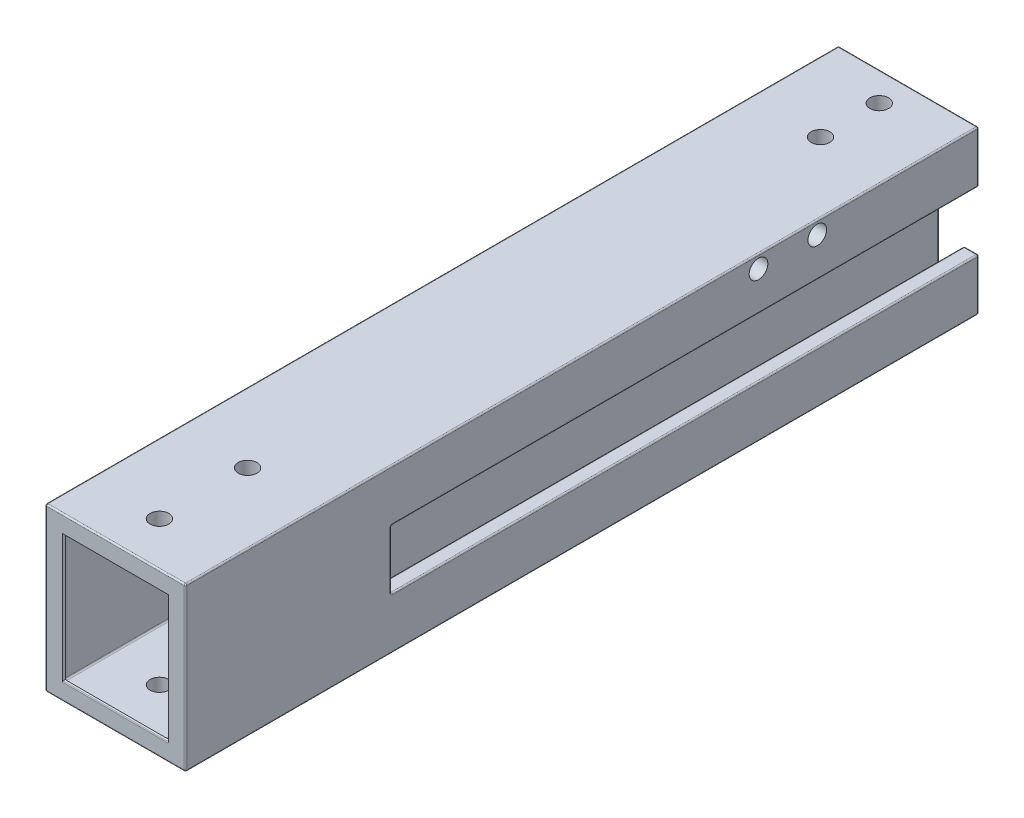
SolidWorks part; units mm, degrees
ref_plane "Front Plane" through (0, 0, 0) normal (0, 0, 1) x (1, 0, 0)
ref_plane "Top Plane" through (0, 0, 0) normal (0, 1, 0) x (1, 0, 0)
ref_plane "Right Plane" through (0, 0, 0) normal (1, 0, 0) x (0, 0, -1)
sketch "Sketch1" plane through (0, 0, 0) normal (0, 0, 1) x (1, 0, 0)
  line L0 (-6.35, -6.35) -> (-6.35, 48.95)
  line L1 (0, 0) -> (35.1, 0) construction
  line L2 (0, 0) -> (0, 42.6) construction
  line L3 (0, 42.6) -> (35.1, 42.6) construction
  line L4 (35.1, 0) -> (35.1, 42.6) construction
  line L5 (-6.35, 48.95) -> (41.45, 48.95)
  line L6 (41.45, -6.35) -> (41.45, 48.95)
  line L7 (-6.35, -6.35) -> (41.45, -6.35)
  dimension "D1" = 35.1
  dimension "D2" = 42.6
  dimension "D3" = 6.35
extrude "Boss-Extrude1" add sketch "Sketch1" against normal blind 270
sketch "Sketch2" plane through (0, 0, 0) normal (0, 0, 1) x (1, 0, 0)
  line L0 (35.1, 42.6) -> (0, 42.6)
  line L1 (0, 42.6) -> (0, 0)
  line L2 (0, 0) -> (35.1, 0)
  line L3 (35.1, 0) -> (35.1, 42.6)
  line L4 (-6.35, -6.35) -> (41.45, -6.35)
  line L5 (41.45, -6.35) -> (41.45, 48.95)
  line L6 (41.45, 48.95) -> (-6.35, 48.95)
  line L7 (-6.35, 48.95) -> (-6.35, -6.35)
  line L8 (-6.35, -6.35) -> (41.45, -6.35) construction
  line L9 (41.45, -6.35) -> (41.45, 48.95) construction
  line L10 (41.45, 48.95) -> (-6.35, 48.95) construction
  line L11 (-6.35, 48.95) -> (-6.35, -6.35) construction
  dimension "D1" = 0
  dimension "D2" = 6.35
extrude "Cut-Extrude1" cut sketch "Sketch2" against normal blind 60
sketch "Sketch3" plane through (0, -6.35, 0) normal (0, -1, 0) x (1, 0, 0)
  line L3 (-6.35, -270) -> (-6.35, 0) construction
  line L4 (-6.35, 0) -> (41.45, 0) construction
  line L5 (-6.35, -270) -> (41.45, -270) construction
  circle A0 centre (17.55, -15) radius 3.175
  circle A3 centre (17.55, -260) radius 3.175
  circle A5 centre (17.55, -240) radius 3.175
  circle A10 centre (17.55, -45) radius 3.175
  dimension "D5" = 30
  dimension "D10" = 6.35
  dimension "D11" = 6.35
  dimension "D7" = 6.35
  dimension "D12" = 6.35
  dimension "D6" = 23.9
  dimension "D8" = 30
  dimension "D9" = 23.9
  dimension "D2" = 15
  dimension "D3" = 10
  dimension "D13" = 23.9
  dimension "D14" = 23.9
extrude "Cut-Extrude2" cut sketch "Sketch3" against normal through all
sketch "Sketch8" plane through (0, 0, -270) normal (0, 0, -1) x (-1, 0, 0)
  line L0 (6.35, 21.3) -> (-41.45, 21.3) construction
  line L1 (6.35, 11.3) -> (1.35, 11.3)
  line L2 (1.35, 11.3) -> (1.35, 1.3)
  line L3 (1.35, 1.3) -> (-7.15, 1.3)
  line L4 (-41.45, -6.35) -> (6.35, -6.35)
  line L5 (6.35, -6.35) -> (6.35, 48.95)
  line L6 (6.35, 48.95) -> (-41.45, 48.95)
  line L7 (-41.45, 48.95) -> (-41.45, -6.35)
  line L8 (-41.45, -6.35) -> (6.35, -6.35) construction
  line L9 (6.35, -6.35) -> (6.35, 48.95) construction
  line L10 (6.35, 48.95) -> (-41.45, 48.95) construction
  line L11 (-41.45, 48.95) -> (-41.45, -6.35) construction
  line L12 (-7.15, 1.3) -> (-7.15, 41.3)
  line L13 (6.35, 31.3) -> (1.35, 31.3)
  line L14 (1.35, 31.3) -> (1.35, 41.3)
  line L15 (1.35, 41.3) -> (-7.15, 41.3)
  line L16 (-17.55, -6.35) -> (-17.55, 48.95) construction
  line L17 (-41.45, 11.3) -> (-36.45, 11.3)
  line L18 (-36.45, 11.3) -> (-36.45, 1.3)
  line L19 (-36.45, 1.3) -> (-27.95, 1.3)
  line L20 (-41.45, 31.3) -> (-36.45, 31.3)
  line L21 (-36.45, 41.3) -> (-27.95, 41.3)
  line L22 (-36.45, 31.3) -> (-36.45, 41.3)
  line L23 (-27.95, 1.3) -> (-27.95, 41.3)
  line L24 (6.35, 31.3) -> (6.35, 11.3)
  line L25 (-41.45, 31.3) -> (-41.45, 11.3)
  point P2 (6.35, 21.3)
  point P16 (-7.15, 21.3)
  dimension "D2" = 10
  dimension "D3" = 20
  dimension "D4" = 8.5
  dimension "D5" = 5
  dimension "D1" = 0
extrude "Cut-Extrude4" cut sketch "Sketch8" against normal blind 200
sketch "Sketch11" plane through (-6.35, 0, 0) normal (-1, 0, 0) x (0, 0, 1)
  line L2 (-270, 48.95) -> (0, 48.95) construction
  line L3 (-270, 48.95) -> (-270, 31.3) construction
  circle A4 centre (-215, 44.55) radius 3.175
  circle A5 centre (-195, 44.55) radius 3.175
  dimension "D2" = 6.35
  dimension "D3" = 6.35
  dimension "D1" = 55
  dimension "D4" = 20
  dimension "D5" = 4.4
  dimension "D6" = 75
extrude "Cut-Extrude5" cut sketch "Sketch11" against normal through all
sketch "Sketch12" plane through (0, 0, -270) normal (0, 0, -1) x (-1, 0, 0)
  line L0 (-41.45, 31.3) -> (-41.45, 11.3) construction
  line L1 (-9.55, 6.3) -> (-25.55, 6.3)
  line L2 (-9.55, 6.3) -> (-9.55, 36.3)
  line L3 (-9.55, 36.3) -> (-25.55, 36.3)
  line L4 (-25.55, 6.3) -> (-25.55, 36.3)
  line L20 (6.35, -6.35) -> (6.35, 11.3)
  line L21 (6.35, 11.3) -> (1.35, 11.3)
  line L22 (1.35, 11.3) -> (1.35, 1.3)
  line L23 (1.35, 1.3) -> (-7.15, 1.3)
  line L24 (-7.15, 1.3) -> (-7.15, 41.3)
  line L25 (-7.15, 41.3) -> (1.35, 41.3)
  line L26 (1.35, 41.3) -> (1.35, 31.3)
  line L27 (1.35, 31.3) -> (6.35, 31.3)
  line L28 (6.35, 31.3) -> (6.35, 48.95)
  line L29 (6.35, 48.95) -> (-41.45, 48.95)
  line L30 (-41.45, 48.95) -> (-41.45, 31.3)
  line L31 (-41.45, 31.3) -> (-36.45, 31.3)
  line L32 (-36.45, 31.3) -> (-36.45, 41.3)
  line L33 (-36.45, 41.3) -> (-27.95, 41.3)
  line L34 (-27.95, 41.3) -> (-27.95, 1.3)
  line L35 (-27.95, 1.3) -> (-36.45, 1.3)
  line L36 (-36.45, 1.3) -> (-36.45, 11.3)
  line L37 (-36.45, 11.3) -> (-41.45, 11.3)
  line L38 (-41.45, 11.3) -> (-41.45, -6.35)
  line L39 (-41.45, -6.35) -> (6.35, -6.35)
  line L40 (6.35, -6.35) -> (6.35, 11.3) construction
  line L41 (6.35, 11.3) -> (1.35, 11.3) construction
  line L42 (1.35, 11.3) -> (1.35, 1.3) construction
  line L43 (1.35, 1.3) -> (-7.15, 1.3) construction
  line L44 (-7.15, 1.3) -> (-7.15, 41.3) construction
  line L45 (-7.15, 41.3) -> (1.35, 41.3) construction
  line L46 (1.35, 41.3) -> (1.35, 31.3) construction
  line L47 (1.35, 31.3) -> (6.35, 31.3) construction
  line L48 (6.35, 31.3) -> (6.35, 48.95) construction
  line L49 (6.35, 48.95) -> (-41.45, 48.95) construction
  line L50 (-41.45, 48.95) -> (-41.45, 31.3) construction
  line L51 (-41.45, 31.3) -> (-36.45, 31.3) construction
  line L52 (-36.45, 31.3) -> (-36.45, 41.3) construction
  line L53 (-36.45, 41.3) -> (-27.95, 41.3) construction
  line L54 (-27.95, 41.3) -> (-27.95, 1.3) construction
  line L55 (-27.95, 1.3) -> (-36.45, 1.3) construction
  line L56 (-36.45, 1.3) -> (-36.45, 11.3) construction
  line L57 (-36.45, 11.3) -> (-41.45, 11.3) construction
  line L58 (-41.45, 11.3) -> (-41.45, -6.35) construction
  line L59 (-41.45, -6.35) -> (6.35, -6.35) construction
  point P10 (-25.55, 21.3)
  point P12 (-17.55, 6.3)
  point P14 (-41.45, 21.3)
  point P16 (-17.55, -6.35)
  dimension "D2" = 30
  dimension "D3" = 16
  dimension "D1" = 0
extrude "Cut-Extrude6" cut sketch "Sketch12" against normal blind 50
chamfer "Chamfer2" distance 0.5 angle 45 8 edges at (0, 21.3, 0) (17.55, 42.6, 0) (17.55, 0, 0) (35.1, 21.3, 0) (17.55, 36.3, -270) (25.55, 21.3, -270) (9.55, 21.3, -270) (17.55, 6.3, -270)
fillet "Fillet1" radius 0.5 77 edges at (17.55, 0, -60) (0, 21.3, -60) (17.55, 42.6, -60) (35.1, 21.3, -60) (41.45, 31.3, -170) (38.95, 31.3, -270) (36.45, 31.3, -170) (36.45, 36.3, -270) (36.45, 41.3, -170) (32.2, 41.3, -270) (36.45, 6.3, -270) (36.45, 1.3, -170) (32.2, 1.3, -270) (41.45, 11.3, -170) (36.45, 11.3, -170) (38.95, 11.3, -270) (27.95, 1.3, -170) (27.95, 41.3, -170) (27.95, 21.3, -270) (38.95, 31.3, -70) (36.45, 36.3, -70) (32.2, 41.3, -70) (27.95, 21.3, -70) (32.2, 1.3, -70) (36.45, 6.3, -70) (38.95, 11.3, -70) (41.45, 21.3, -70) (17.55, 6.3, -220) (25.55, 21.3, -220) (17.55, 36.3, -220) (9.55, 21.3, -220) (-1.35, 41.3, -170) (2.9, 41.3, -270) (-1.35, 6.3, -270) (-1.35, 1.3, -170) (2.9, 1.3, -270) (7.15, 41.3, -170) (7.15, 1.3, -170) (7.15, 21.3, -270) (-6.35, 31.3, -170) (-1.35, 31.3, -170) (-3.85, 31.3, -270) (-1.35, 11.3, -170) (-6.35, 11.3, -170) (-3.85, 11.3, -270) (-3.85, 11.3, -70) (-1.35, 6.3, -70) (2.9, 1.3, -70) (7.15, 21.3, -70) (2.9, 41.3, -70) (-1.35, 36.3, -70) (-3.85, 31.3, -70) (-6.35, 21.3, -70) (41.45, 48.95, -135) (-6.35, 48.95, -135) (-6.35, -6.35, -135) (41.45, -6.35, -135) (0, 42.6, -30.25) (35.1, 42.6, -30.25) (35.1, 0, -30.25) (0, 0, -30.25) (17.55, 48.95, 0) (41.45, 21.3, 0) (17.55, -6.35, 0) (-6.35, 21.3, 0) (41.45, 2.475, -270) (17.55, -6.35, -270) (-6.35, 2.475, -270) (41.45, 40.125, -270) (-1.35, 36.3, -270) (-6.35, 40.125, -270) (17.55, 48.95, -270) (17.55, -0.5, 0) (25.55, 6.3, -244.75) (9.55, 6.3, -244.75) (25.55, 36.3, -244.75) (9.55, 36.3, -244.75)
